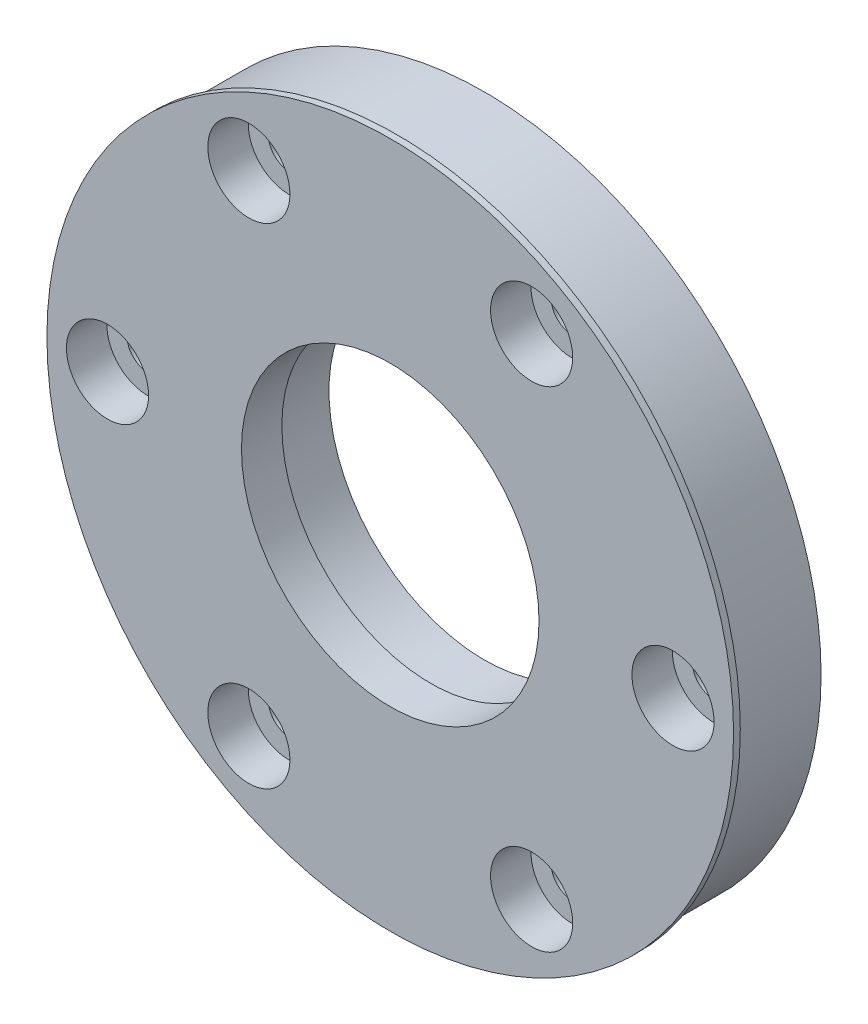
SolidWorks part; units mm, degrees
material "ABS"
ref_plane "Front Plane" through (0, 0, 0) normal (0, 0, 1) x (1, 0, 0)
ref_plane "Top Plane" through (0, 0, 0) normal (0, 1, 0) x (1, 0, 0)
ref_plane "Right Plane" through (0, 0, 0) normal (1, 0, 0) x (0, 0, -1)
sketch "Output Master Sketch" plane through (0, 0, 0) normal (0, 0, 1) x (1, 0, 0)
  circle A0 centre (0, 0) radius 21 construction
  circle A1 centre (21, 0) radius 3.05 construction
  circle A2 centre (10.5, -18.1865) radius 3.05 construction
  circle A3 centre (-10.5, -18.1865) radius 3.05 construction
  circle A4 centre (-21, 0) radius 3.05 construction
  circle A5 centre (-10.5, 18.1865) radius 3.05 construction
  circle A6 centre (10.5, 18.1865) radius 3.05 construction
  circle A7 centre (0, 0) radius 25
  point P17 (0, 0)
sketch "Sketch2" plane through (0, 0, 0) normal (0, 0, 1) x (1, 0, 0)
  circle A0 centre (0, 0) radius 25
  circle A1 centre (0, 0) radius 25 construction
extrude "Boss-Extrude1" add sketch "Sketch2" along normal blind 7
sketch "Sketch3" plane through (0, 0, 7) normal (0, 0, 1) x (1, 0, 0)
  circle A0 centre (-21, 0) radius 3.05
  circle A1 centre (-21, 0) radius 3.05 construction
  circle A2 centre (-10.5, 18.1865) radius 3.05
  circle A3 centre (10.5, 18.1865) radius 3.05
  circle A4 centre (21, 0) radius 3.05
  circle A5 centre (10.5, -18.1865) radius 3.05
  circle A6 centre (-10.5, -18.1865) radius 3.05
  point P18 (0, 0)
  dimension "D1" = 6.1
  dimension "D2" = 6
extrude "Dowel Pin Cutout" cut sketch "Sketch3" against normal blind 3
sketch "Sketch4" plane through (0, 0, 7) normal (0, 0, 1) x (1, 0, 0)
  circle A0 centre (0, 0) radius 25
  circle A1 centre (0, 0) radius 25.5
  circle A3 centre (0, 0) radius 25 construction
  dimension "D1" = 0.5
extrude "Main Housing Bearing Retainer" add sketch "Sketch4" against normal blind 0.5
sketch "Sketch5" plane through (0, 0, 0) normal (0, 0, -1) x (-1, 0, 0)
  circle A0 centre (-21, 0) radius 1.55
  circle A1 centre (-10.5, 18.1865) radius 1.55
  circle A2 centre (10.5, 18.1865) radius 1.55
  circle A3 centre (21, 0) radius 1.55
  circle A4 centre (10.5, -18.1865) radius 1.55
  circle A5 centre (-10.5, -18.1865) radius 1.55
  point P15 (0, 0)
  dimension "D1" = 3.1
  dimension "D2" = 6
extrude "M3 Thru" cut sketch "Sketch5" against normal through all
sketch "Sketch6" plane through (0, 0, 0) normal (0, 0, -1) x (-1, 0, 0)
  circle A0 centre (-21, 0) radius 3
  circle A1 centre (-10.5, 18.1865) radius 3
  circle A2 centre (10.5, 18.1865) radius 3
  circle A3 centre (21, 0) radius 3
  circle A4 centre (10.5, -18.1865) radius 3
  circle A5 centre (-10.5, -18.1865) radius 3
  point P15 (0, 0)
  dimension "D1" = 6
  dimension "D2" = 6
extrude "M3 Button Head Cutout" cut sketch "Sketch6" against normal blind 1.7
sketch "Sketch8" plane through (0, 0, 7) normal (0, 0, 1) x (1, 0, 0)
  circle A0 centre (0, 0) radius 11.55
  dimension "D1" = 23.1
extrude "Input Shaft Bearing Cutout" cut sketch "Sketch8" against normal through all
sketch "Sketch9" plane through (0, 0, 0) normal (0, 0, -1) x (-1, 0, 0)
  circle A0 centre (0, 0) radius 11.55
  circle A1 centre (0, 0) radius 11.05
  circle A2 centre (0, 0) radius 11.55 construction
  dimension "D1" = 0.5
extrude "Input Shaft Bearing Retainer" add sketch "Sketch9" along normal blind 3 from surface starting at face at (11.55, 0, 7)
